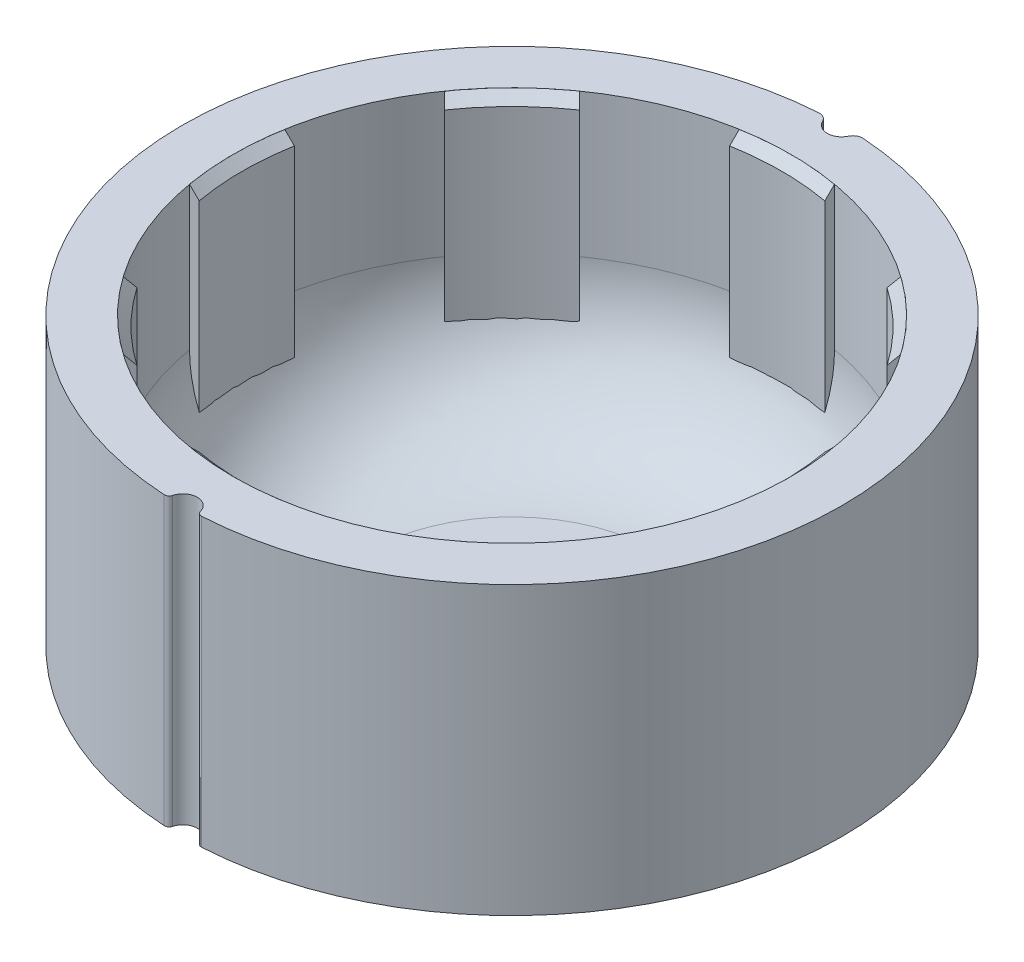
SolidWorks part; units mm, degrees
other "Markup1"
sketch "Sketch4"
other "Markup5"
sketch "Sketch8" plane through (34.5, 25, 34.4428) normal (0.0041, 0.9851, 0.1719) x (0.981, -0.0374, 0.1906)
other "Markup6"
sketch "Sketch9" plane through (34.5, 25, 34.4428) normal (0.0041, 0.9851, 0.1719) x (0.981, -0.0374, 0.1906)
other "Markup7"
sketch "Sketch10" plane through (-34.5, 25, 34.4428) normal (-0.125, 0.9874, 0.0969) x (0.5933, -0.0039, 0.805)
other "Markup8"
sketch "Sketch11" plane through (34.5, 30, -34.4259) normal (0.1773, 0.9842, -0.0012) x (-0.272, 0.0478, -0.9611)
ref_plane "Front Plane" through (0, 0, 0) normal (0, 0, 1) x (1, 0, 0)
ref_plane "Top Plane" through (0, 0, 0) normal (0, 1, 0) x (1, 0, 0)
ref_plane "Right Plane" through (0, 0, 0) normal (1, 0, 0) x (0, 0, -1)
sketch "Sketch1" plane through (0, 0, 0) normal (0, 1, 0) x (1, 0, 0)
  line L3 (0, 0.002) -> (0, 3.7877) construction
  line L4 (0, 3.7877) -> (2.417, 3.7877)
  line L5 (0, 3.7877) -> (-2.417, 3.7877)
  arc A0 (1.9642, -34.442) -> (34.1982, 4.5552) centre (0, 0.002) ccw
  arc A2 (-2.417, 3.7877) -> (2.417, 3.7877) centre (0, 0.002) ccw
  circle A3 centre (0, 0.002) radius 34.5 construction
  arc A7 (-1.3541, 33.8562) -> (1.3541, 33.8562) centre (0, 34.5015) ccw
  arc A8 (34.1982, 4.5552) -> (2.3241, 34.4236) centre (0, 0.002) ccw
  arc A9 (-2.3241, 34.4236) -> (-34.1982, 4.5552) centre (0, 0.002) ccw
  arc A10 (-34.1982, 4.5552) -> (-1.9642, -34.442) centre (0, 0.002) ccw
  arc A11 (1.3541, 33.8562) -> (2.3241, 34.4236) centre (2.2568, 33.4259) cw
  arc A12 (-1.3541, 33.8562) -> (-2.3241, 34.4236) centre (-2.2568, 33.4259) ccw
  arc A13 (1.4518, -34.0686) -> (-1.4518, -34.0686) centre (0, -34.4457) ccw
  arc A14 (1.4518, -34.0686) -> (1.9642, -34.442) centre (1.9358, -33.9428) ccw
  arc A15 (-1.4518, -34.0686) -> (-1.9642, -34.442) centre (-1.9358, -33.9428) cw
  point P15 (1.4997, 34.4694)
  dimension "D2" = 4.834
  dimension "D3" = 4.4915
  dimension "D4" = 34.5
  dimension "D5" = 1
  dimension "D6" = 1.5
  dimension "D7" = 0.5
  dimension "D11" = 1.4997
sketch "Sketch2" plane through (0, 0, 0) normal (0, 1, 0) x (1, 0, 0)
  line L0 (0, 29.2) -> (0, 28.2) construction
  line L1 (-4.9816, 28.7719) -> (0, 29.2) construction
  line L2 (0, 29.2) -> (4.9816, 28.7719) construction
  line L3 (-4.9816, 28.7719) -> (-4.9816, 27.7565)
  line L6 (4.9816, 27.7565) -> (4.9816, 28.7719)
  circle A16 centre (0, 0) radius 29.2
  arc A18 (-4.9816, 27.7565) -> (4.9816, 27.7565) centre (0, 0) cw
  point P3 (0, 28.2)
  dimension "D1" = 58.4
  dimension "D2" = 5
  dimension "D3" = 1
extrude "Boss-Extrude1" add sketch "Sketch1" along normal blind 30 contours A10 A0 A8 A7 A9 A2 L5 L4 | L5 A2 L4 region at (0, 0, 0.1522) region at (2.2155, 0, 33.5591)
extrude "Cut-Extrude2" cut sketch "Sketch2" along normal up to next from offset 1 contours A16 | A16 region at (0, 0, 0.1072)
extrude "Boss-Extrude2" add sketch "Sketch2<2>" along normal up to surface (30 mm away) separate body contours A16 region at (0, 0, -28.5546) up to face at (0, 30, 29.2)
sketch "Sketch2<2>" plane through (0, 0, 0) normal (0, 1, 0) x (1, 0, 0) same geometry as "Sketch2"
chamfer "Chamfer2" distance 1 angle 45 1 edges at (0, 30, -28.2)
pattern_circular "CirPattern2" count 8 over 360 about axis through (0, 30, 0) along (0, 1, 0) of bodies 106
fillet "Fillet2" radius 14 1 edges at (0, 1, 29.2)
